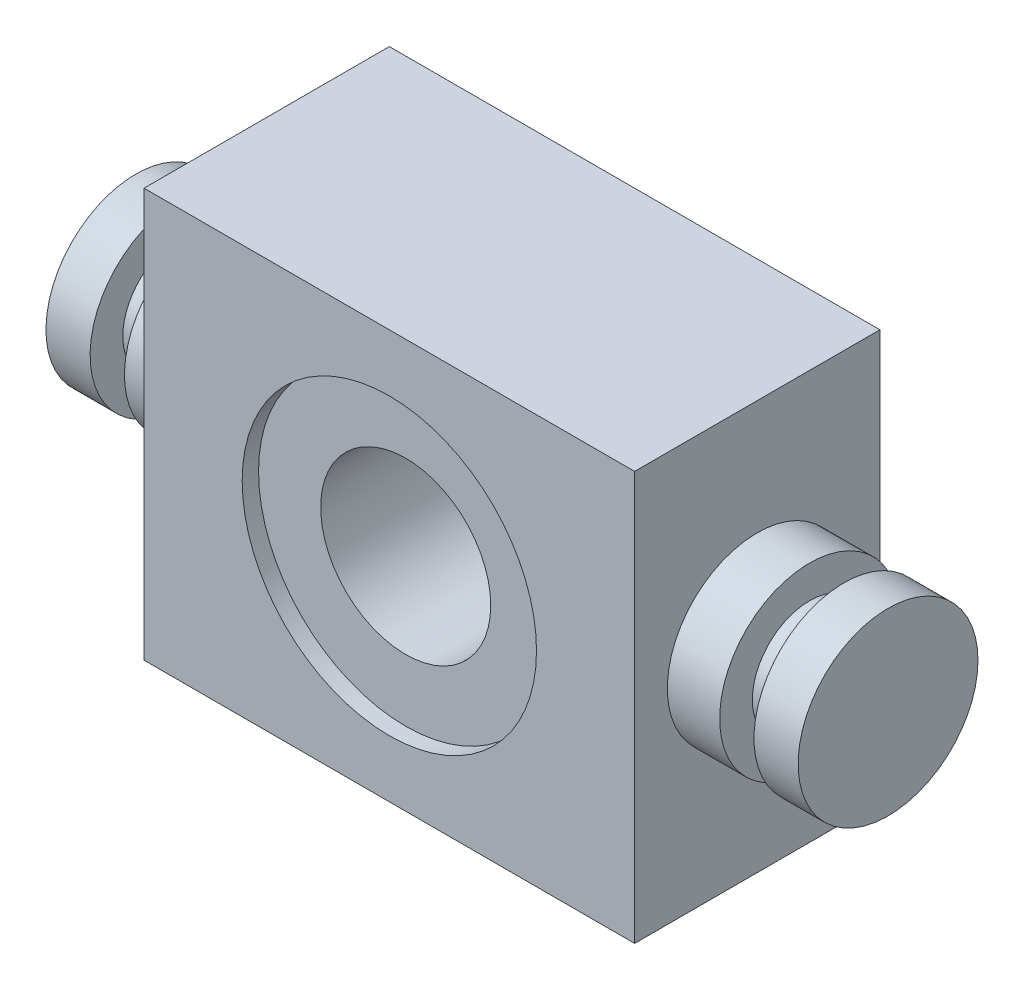
SolidWorks part; units mm, degrees
ref_plane "Front Plane" through (0, 0, 0) normal (0, 0, 1) x (1, 0, 0)
ref_plane "Top Plane" through (0, 0, 0) normal (0, 1, 0) x (1, 0, 0)
ref_plane "Right Plane" through (0, 0, 0) normal (1, 0, 0) x (0, 0, -1)
sketch "Sketch1" plane through (0, 0, 0) normal (0, 0, 1) x (1, 0, 0)
  line L0 (-56.7178, 0) -> (62.3379, 0) construction
  line L1 (0, 56.369) -> (0, -55.1831) construction
  line L2 (-75, -62.5) -> (75, -62.5)
  line L7 (75, -62.5) -> (75, 62.5)
  line L8 (75, 62.5) -> (-75, 62.5)
  line L9 (-75, 62.5) -> (-75, -62.5)
  circle A0 centre (0, 0) radius 45
  circle A1 centre (0, 0) radius 26
  dimension "D2" = 90
  dimension "D4" = 52
  dimension "D1" = 150
  dimension "D3" = 125
extrude "Boss-Extrude2" add sketch "Sketch1" along normal blind 75 contours L8 L9 L2 L7 A0 region at (-73.0474, 0, 0)
extrude "Boss-Extrude3" add sketch "Sketch1<5>" along normal blind 70 contours A0 A1 region at (-43.7272, 0, 0)
sketch "Sketch1<5>" plane through (0, 0, 0) normal (0, 0, 1) x (1, 0, 0) same geometry as "Sketch1"
sketch "Sketch6" plane through (75, 0, 0) normal (1, 0, 0) x (0, 0, -1)
  circle A0 centre (-37.5, 0) radius 27.5
extrude "Boss-Extrude5" add sketch "Sketch6" along normal blind 16
sketch "Sketch7" plane through (91, 0, 0) normal (1, 0, 0) x (0, 0, -1)
  circle A2 centre (-37.5, 0) radius 17.5
  circle A3 centre (-37.5, 0) radius 17.5
  dimension "D1" = 10
extrude "Boss-Extrude6" add sketch "Sketch7" along normal blind 10.5
sketch "Sketch8" plane through (101.5, 0, 0) normal (1, 0, 0) x (0, 0, -1)
  circle A2 centre (-37.5, 0) radius 27.5
  circle A3 centre (-37.5, 0) radius 27.5
  dimension "D1" = 10
extrude "Boss-Extrude7" add sketch "Sketch8" along normal blind 13.5
sketch "Sketch9" plane through (-75, 0, 0) normal (-1, 0, 0) x (0, 0, 1)
  circle A0 centre (37.5, 0) radius 27.5
  dimension "D1" = 55
extrude "Boss-Extrude8" add sketch "Sketch9" along normal blind 16
sketch "Sketch10" plane through (-91, 0, 0) normal (-1, 0, 0) x (0, 0, 1)
  line L0 (37.5, 27.5) -> (37.5, -42.2256) construction
  line L1 (10, 0) -> (65, 0) construction
  circle A0 centre (37.5, 0) radius 27.5 construction
  circle A1 centre (37.5, 0) radius 27.5 construction
  circle A2 centre (37.5, 0) radius 17.5
  dimension "D1" = 35
extrude "Boss-Extrude9" add sketch "Sketch10" along normal blind 10.5
sketch "Sketch11" plane through (-101.5, 0, 0) normal (-1, 0, 0) x (0, 0, 1)
  circle A0 centre (37.5, 0) radius 27.5
extrude "Boss-Extrude10" add sketch "Sketch11" along normal blind 13.5
